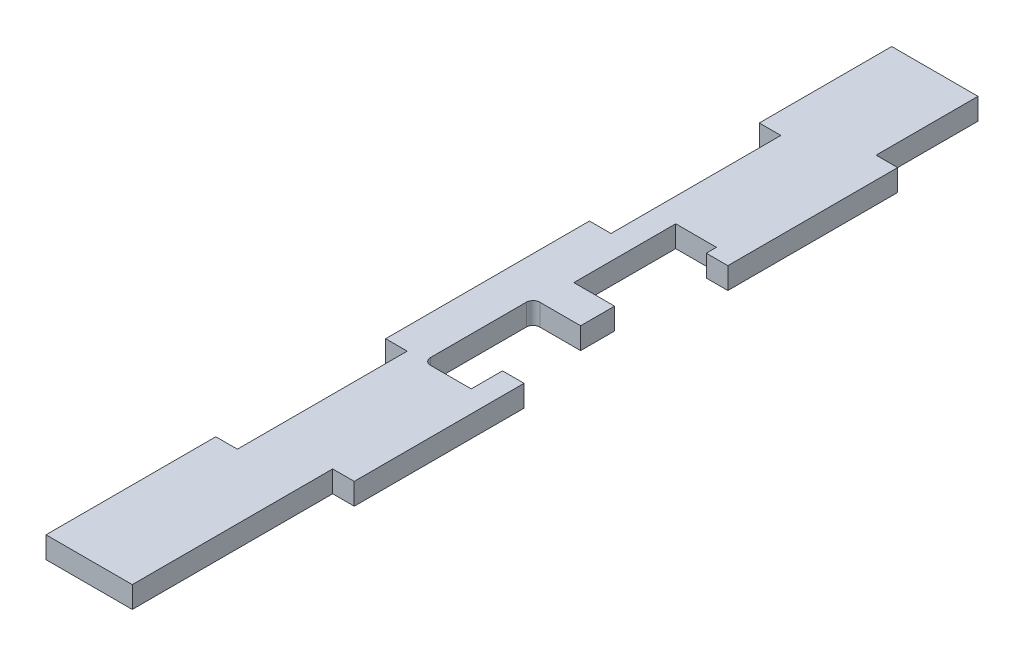
SolidWorks part; units mm, degrees
material "Balsa"
ref_plane "Front Plane" through (0, 0, 0) normal (0, 0, 1) x (1, 0, 0)
ref_plane "Top Plane" through (0, 0, 0) normal (0, 1, 0) x (1, 0, 0)
ref_plane "Right Plane" through (0, 0, 0) normal (1, 0, 0) x (0, 0, -1)
sketch "Sketch2" plane through (0, 0, 0) normal (0, 1, 0) x (1, 0, 0)
  line L13 (0, 0) -> (25.4, 0)
  line L14 (0, 0) -> (0, 249)
  line L15 (0, 249) -> (25.4, 249)
  line L16 (25.4, 0) -> (25.4, 59)
  line L17 (25.4, 59) -> (31.75, 59)
  line L19 (25.4, 109) -> (31.75, 109)
  line L20 (31.75, 59) -> (31.75, 109)
  line L21 (25.4, 169) -> (31.75, 169)
  line L22 (31.75, 169) -> (31.75, 219)
  line L23 (25.4, 219) -> (31.75, 219)
  line L25 (25.4, 219) -> (25.4, 249)
  line L26 (25.4, 109) -> (25.4, 169)
  dimension "D1" = 25.4
  dimension "D2" = 249
  dimension "D3" = 6.35
  dimension "D4" = 50
  dimension "D5" = 59
  dimension "D6" = 2
  dimension "D7" = 30
extrude "Boss-Extrude1" add sketch "Sketch2" along normal blind 6.35
sketch "Sketch3" plane through (0, 6.35, 0) normal (0, 1, 0) x (1, 0, 0)
  line L5 (25.4, 109) -> (25.4, 169) construction
  line L6 (25.4, 132) -> (11.4, 132)
  line L7 (25.4, 132) -> (25.4, 99.8)
  line L8 (25.4, 99.8) -> (11.4, 99.8)
  line L9 (11.4, 132) -> (11.4, 99.8)
  line L10 (0, 0) -> (25.4, 0) construction
  line L12 (25.4, 142) -> (13.4, 142)
  line L13 (25.4, 142) -> (25.4, 172)
  line L14 (25.4, 172) -> (13.4, 172)
  line L15 (13.4, 142) -> (13.4, 172)
  dimension "D4" = 30
  dimension "D1" = 99.8
  dimension "D2" = 14
  dimension "D3" = 32.2
  dimension "D5" = 12
  dimension "D6" = 10
extrude "Cut-Extrude1" cut sketch "Sketch3" against normal through all
fillet "Fillet1" radius 2 2 edges at (11.4, 3.175, -99.8) (11.4, 3.175, -132)
sketch "Sketch4" plane through (0, 6.35, 0) normal (0, 1, 0) x (1, 0, 0)
  line L0 (0, 249) -> (0, 0) construction
  line L1 (0, 50) -> (6.35, 50)
  line L2 (0, 50) -> (0, 100)
  line L3 (0, 100) -> (6.35, 100)
  line L4 (6.35, 50) -> (6.35, 100)
  line L5 (0, 0) -> (25.4, 0) construction
  line L6 (0, 160) -> (0, 210)
  line L7 (0, 160) -> (6.35, 160)
  line L8 (6.35, 160) -> (6.35, 210)
  line L9 (0, 210) -> (6.35, 210)
  line L10 (25.4, 249) -> (0, 249) construction
  dimension "D1" = 6.35
  dimension "D2" = 50
  dimension "D3" = 50
  dimension "D5" = 39
  dimension "D4" = 2
extrude "Cut-Extrude2" cut sketch "Sketch4" against normal through all
